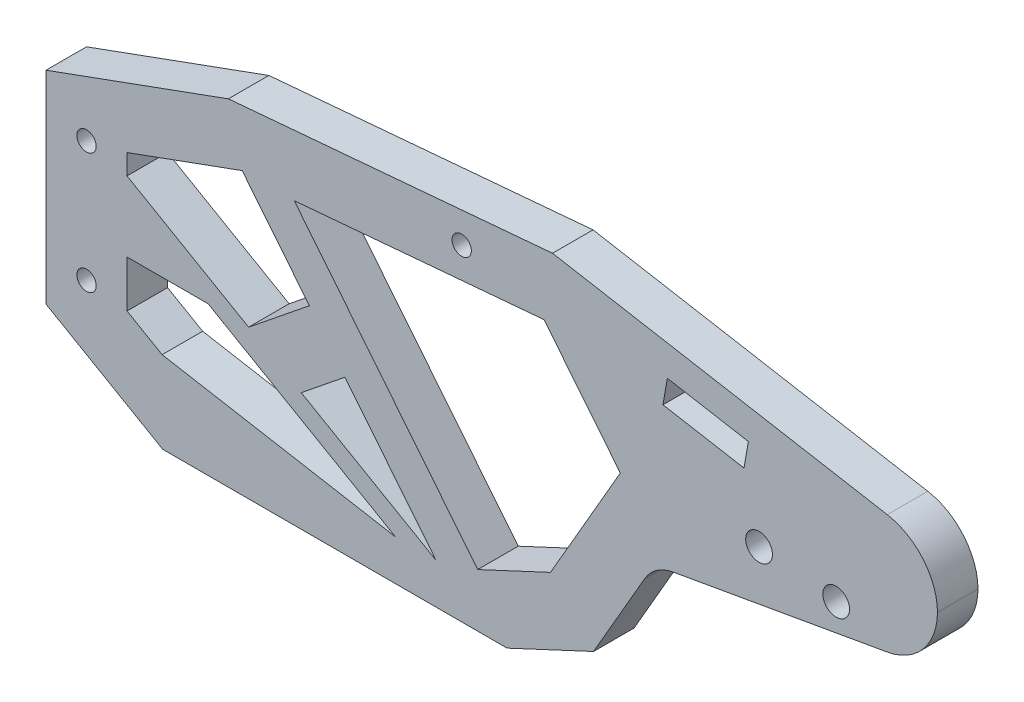
SolidWorks part; units mm, degrees
ref_plane "Plan de face" through (0, 0, 0) normal (0, 0, 1) x (1, 0, 0)
ref_plane "Plan de dessus" through (0, 0, 0) normal (0, 1, 0) x (1, 0, 0)
ref_plane "Plan de droite" through (0, 0, 0) normal (1, 0, 0) x (0, 0, -1)
sketch "Esquisse1" plane through (0, 0, 0) normal (0, 0, 1) x (1, 0, 0)
  line L1 (0, 0) -> (220, 0)
  line L2 (0, 0) -> (0, 90)
  line L3 (0, 90) -> (220, 90)
  line L4 (220, 0) -> (220, 90)
  dimension "D1" = 90
  dimension "D2" = 220
extrude "Boss.-Extru.1" add sketch "Esquisse1" along normal blind 10 contours L3 L4 L1 L2
sketch "Esquisse2" plane through (0, 0, 10) normal (0, 0, 1) x (1, 0, 0)
  line L0 (220, 73.2489) -> (125, 90)
  line L1 (220, 0) -> (220, 90) construction
  line L2 (0, 90) -> (220, 90) construction
  line L3 (125, 90) -> (45, 83.0009)
  line L4 (45, 83.0009) -> (0, 66.6222)
  line L5 (0, 0) -> (0, 90) construction
  line L6 (0, 66.6222) -> (0, 16.6222)
  line L7 (0, 16.6222) -> (28.7906, 0)
  line L8 (0, 0) -> (220, 0) construction
  line L9 (28.7906, 0) -> (113.7906, 0)
  line L10 (113.7906, 0) -> (135.1213, 9.9467)
  line L11 (135.1213, 9.9467) -> (150.1213, 35.9274)
  line L12 (150.1213, 35.9274) -> (220, 48.2489)
  line L13 (220, 48.2489) -> (220, 73.2489)
  point P15 (130.4217, 7.7552)
  point P19 (133.6658, 9.268)
  dimension "D1" = 10
  dimension "D2" = 10
  dimension "D3" = 25
  dimension "D4" = 30
  dimension "D5" = 15
  dimension "D6" = 5
  dimension "D7" = 25
  dimension "D8" = 50
  dimension "D9" = 45
  dimension "D10" = 95
  dimension "D11" = 15
  dimension "D12" = 85
extrude "Enlèv. mat.-Extru.1" cut sketch "Esquisse2" against normal through all flip side to cut
sketch "Esquisse3" plane through (0, 0, 10) normal (0, 0, 1) x (1, 0, 0)
  line L0 (124.4956, 21.5425) -> (141.7327, 51.398)
  line L1 (141.7327, 51.398) -> (122.9121, 74.76)
  line L2 (122.9121, 74.76) -> (61.2631, 69.3664)
  line L3 (61.2631, 69.3664) -> (106.537, 13.1682)
  line L4 (96.248, 10) -> (73.7768, 37.8934)
  line L5 (73.7768, 37.8934) -> (62.9886, 29.2023)
  line L6 (62.9886, 29.2023) -> (96.248, 10)
  line L8 (20, 25.1543) -> (20, 36.7013)
  line L9 (20, 36.7013) -> (40, 36.7013)
  line L10 (40, 36.7013) -> (86.248, 10)
  line L11 (20, 54.0218) -> (49.9982, 36.7023)
  line L12 (49.9982, 36.7023) -> (65, 48.7879)
  line L13 (65, 48.7879) -> (48.4217, 69.3664)
  line L14 (48.4217, 69.3664) -> (20, 59.0218)
  line L15 (20, 59.0218) -> (20, 54.0218)
  line L16 (125, 90) -> (45, 83.0009) construction
  line L17 (135.1213, 9.9467) -> (150.1213, 35.9274) construction
  line L18 (0, 16.6222) -> (28.7906, 0) construction
  line L19 (113.7906, 0) -> (135.1213, 9.9467) construction
  line L20 (28.6603, 20.1543) -> (86.248, 10)
  line L21 (45, 83.0009) -> (0, 66.6222) construction
  line L22 (0, 16.6222) -> (0, 66.6222) construction
  line L23 (106.537, 13.1682) -> (124.4956, 21.5425)
  line L24 (28.7906, 0) -> (113.7906, 0) construction
  line L25 (20, 25.1543) -> (28.6603, 20.1543)
  dimension "D1" = 10
  dimension "D2" = 30
  dimension "D3" = 5
  dimension "D4" = 20
  dimension "D5" = 45
  dimension "D6" = 10
  dimension "D7" = 20
  dimension "D9" = 15
  dimension "D10" = 5
  dimension "D11" = 15
  dimension "D12" = 15
  dimension "D13" = 20
  dimension "D14" = 15
  dimension "D15" = 10
  dimension "D16" = 20
extrude "Enlèv. mat.-Extru.2" cut sketch "Esquisse3" against normal through all
fillet "Congé1" radius 15 2 edges at (220, 73.2489, 5) (220, 48.2489, 5)
sketch "Esquisse4" plane through (0, 0, 10) normal (0, 0, 1) x (1, 0, 0)
  line L0 (194.9998, 50.5372) -> (194.9998, 77.6572) construction
  line L1 (207.6047, 75.4346) -> (125, 90) construction
  circle A0 centre (194.9998, 50.5372) radius 3.305
  circle A1 centre (175.9723, 52.7427) radius 3.305
  point P8 (0, 0)
  dimension "D1" = 6.61
  dimension "D2" = 25
  dimension "D4" = 19.0274
  dimension "D3" = 27.12
  dimension "D5" = 2.2056
extrude "Enlèv. mat.-Extru.3" cut sketch "Esquisse4" against normal through all
hole_wizard "Perçage pour écrous auto-bloquants 300® #6 (SP)1" positions "Esquisse5" profile "Esquisse6" hole size "#6-32" standard "PEM® Inch" end condition through all
sketch "Esquisse5" plane through (0, 0, 10) normal (0, 0, 1) x (1, 0, 0)
  line L21 (102.9121, 73.0103) -> (102.5846, 80.5103) construction
  line L22 (102.5846, 80.5103) -> (102.2572, 88.0103) construction
  line L24 (122.9121, 74.76) -> (61.2631, 69.3664) construction
  line L25 (125, 90) -> (45, 83.0009) construction
  point P41 (102.5846, 80.5103)
  point P59 (108.3147, 73.4829)
  point P62 (115.7388, 89.1898)
  point P65 (107.8604, 80.9914)
  point P66 (105.565, 88.2997)
  point P67 (104.0807, 80.6658)
  point P68 (102.2305, 88.0079)
  dimension "D1" = 7.5
  dimension "D2" = 20
sketch "Esquisse6" plane through (102.5846, 80.5103, 10) normal (1, 0, 0) x (0, -1, 0)
  line L0 (0, 0) -> (0, 10)
  line L1 (0, 10) -> (2.3812, 10)
  line L2 (2.3812, 10) -> (2.3812, 0)
  line L5 (2.3812, 0) -> (0, 0)
  line L11 (0, -6.35) -> (0, 107.95) construction
  dimension "Diamètre du perçage jusqu'au prochain" = 4.7625
  dimension "Profondeur du perçage jusqu'au prochain" = 10
hole_wizard "Perçage pour écrous auto-bloquants 300® #6 (SP)2" positions "Esquisse8" profile "Esquisse9" hole size "#6-32" standard "PEM® Inch" end condition through all
sketch "Esquisse8" plane through (0, 0, 10) normal (0, 0, 1) x (1, 0, 0)
  line L0 (10, 56.5218) -> (0, 56.5218) construction
  line L1 (0, 16.6222) -> (0, 66.6222) construction
  line L3 (10, 56.5218) -> (20, 56.5218) construction
  line L4 (20, 59.0218) -> (20, 54.0218) construction
  line L6 (10, 56.5218) -> (10, 26.7227) construction
  point P0 (10, 56.5218)
  point P2 (10, 26.7227)
  point P23 (0, 41.6222)
  point P24 (10, 41.6222)
  point P26 (20, 56.5218)
sketch "Esquisse9" plane through (10, 56.5218, 10) normal (1, 0, 0) x (0, -1, 0)
  line L0 (0, 0) -> (0, 10)
  line L1 (0, 10) -> (2.3812, 10)
  line L2 (2.3812, 10) -> (2.3812, 0)
  line L5 (2.3812, 0) -> (0, 0)
  line L11 (0, -6.35) -> (0, 107.95) construction
  dimension "Diamètre du perçage jusqu'au prochain" = 4.7625
  dimension "Profondeur du perçage jusqu'au prochain" = 10
sketch "Esquisse10" plane through (0, 0, 10) normal (0, 0, 1) x (1, 0, 0)
  line L0 (153.346, 77.4471) -> (152.252, 71.2428)
  line L1 (153.346, 77.4471) -> (173.3376, 73.922)
  line L2 (152.252, 71.2428) -> (172.2436, 67.7177)
  line L3 (173.3376, 73.922) -> (172.2436, 67.7177)
  line L4 (162.2478, 69.4802) -> (194.9998, 50.5372) construction
  line L6 (207.6047, 75.4346) -> (125, 90) construction
  dimension "D1" = 20.3
  dimension "D2" = 6.3
  dimension "D3" = 37.8355
  dimension "D4" = 7.44
extrude "Enlèv. mat.-Extru.4" cut sketch "Esquisse10" against normal blind 10 contours L1 L3 L2 L0
fillet "Congé2" radius 10 1 edges at (150.1213, 35.9274, 5)
